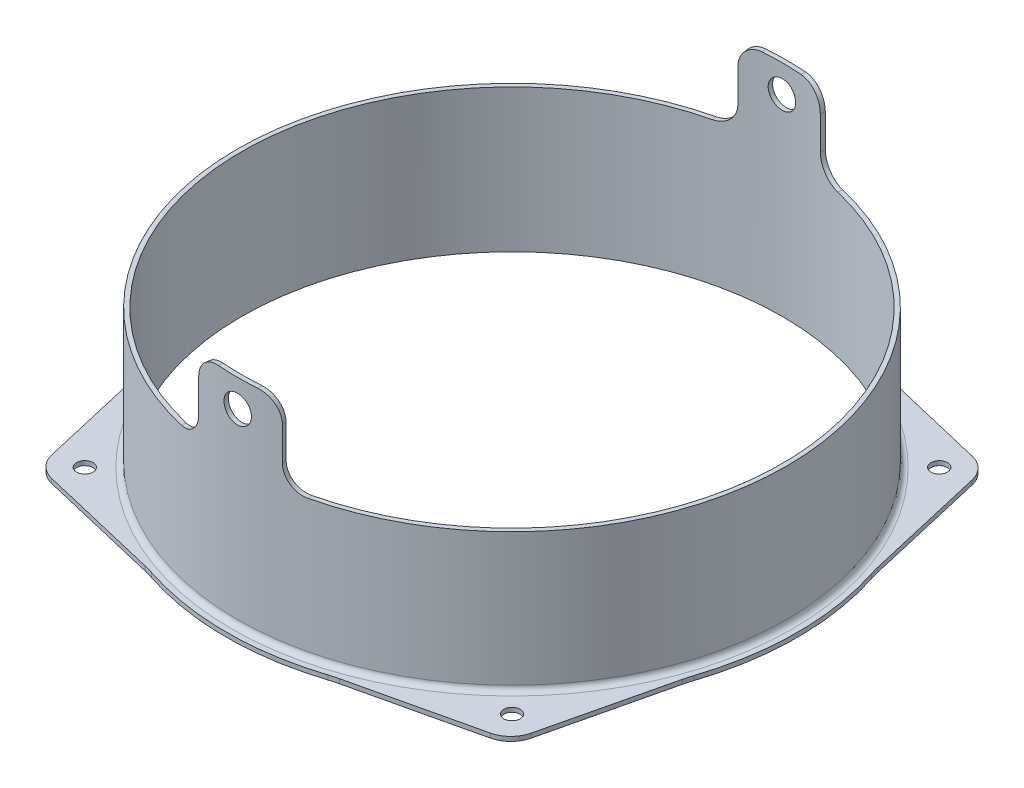
SolidWorks part; units mm, degrees
material "Stainless Steel (ferritic)"
ref_plane "Front Plane" through (0, 0, 0) normal (0, 0, 1) x (1, 0, 0)
ref_plane "Top Plane" through (0, 0, 0) normal (0, 1, 0) x (1, 0, 0)
ref_plane "Right Plane" through (0, 0, 0) normal (1, 0, 0) x (0, 0, -1)
sketch "Sketch1" plane through (0, 0, 0) normal (0, 1, 0) x (1, 0, 0)
  line L0 (17.8971, 48.9297) -> (40.1493, 43.6512)
  line L1 (43.8664, 39.9141) -> (49.0252, 17.6338)
  line L2 (48.9297, -17.8971) -> (43.6512, -40.1493)
  line L3 (39.9141, -43.8664) -> (17.6338, -49.0252)
  line L4 (-17.8971, -48.9297) -> (-40.1493, -43.6512)
  line L5 (-43.8664, -39.9141) -> (-49.0252, -17.6338)
  line L6 (-48.9297, 17.8971) -> (-43.6512, 40.1493)
  line L7 (-39.9141, 43.8664) -> (-17.6338, 49.0252)
  line L8 (0.1397, 51.9998) -> (-0.1397, -51.9998) construction
  line L9 (-51.9998, 0.1397) -> (51.9998, -0.1397) construction
  line L10 (0, 38.8907) -> (0, -38.8907) construction
  line L11 (-38.8907, 38.8907) -> (38.8907, 38.8907) construction
  line L12 (-38.8907, 38.8907) -> (-38.8907, -38.8907) construction
  line L13 (-38.8907, -38.8907) -> (38.8907, -38.8907) construction
  line L14 (38.8907, 38.8907) -> (38.8907, -38.8907) construction
  line L15 (-38.8907, 0) -> (38.8907, 0) construction
  circle A0 centre (0, 0) radius 49.2
  circle A1 centre (0, 0) radius 50
  arc A2 (-17.6338, 49.0252) -> (-15.9939, 49.4792) centre (-22.1454, 68.5097) ccw
  arc A3 (0.1397, 51.9998) -> (-15.9939, 49.4792) centre (0, 0) ccw
  arc A4 (16.2596, 49.3926) -> (0.1397, 51.9998) centre (0, 0) ccw
  arc A5 (16.2596, 49.3926) -> (17.8971, 48.9297) centre (22.5132, 68.3897) ccw
  arc A6 (43.8664, 39.9141) -> (40.1493, 43.6512) centre (38.9952, 38.7862) ccw
  arc A7 (49.0252, 17.6338) -> (49.4792, 15.9939) centre (68.5097, 22.1454) ccw
  arc A8 (49.3926, -16.2596) -> (49.4792, 15.9939) centre (0, 0) ccw
  arc A9 (49.3926, -16.2596) -> (48.9297, -17.8971) centre (68.3897, -22.5132) ccw
  arc A10 (39.9141, -43.8664) -> (43.6512, -40.1493) centre (38.7862, -38.9952) ccw
  arc A11 (17.6338, -49.0252) -> (15.9939, -49.4792) centre (22.1454, -68.5097) ccw
  arc A12 (-16.2596, -49.3926) -> (15.9939, -49.4792) centre (0, 0) ccw
  arc A13 (-16.2596, -49.3926) -> (-17.8971, -48.9297) centre (-22.5132, -68.3897) ccw
  arc A14 (-43.8664, -39.9141) -> (-40.1493, -43.6512) centre (-38.9952, -38.7862) ccw
  arc A15 (-49.0252, -17.6338) -> (-49.4792, -15.9939) centre (-68.5097, -22.1454) ccw
  arc A16 (-49.3926, 16.2596) -> (-49.4792, -15.9939) centre (0, 0) ccw
  arc A17 (-49.3926, 16.2596) -> (-48.9297, 17.8971) centre (-68.3897, 22.5132) ccw
  arc A18 (-39.9141, 43.8664) -> (-43.6512, 40.1493) centre (-38.7862, 38.9952) ccw
  circle A21 centre (-38.8907, 38.8907) radius 1.5
  circle A22 centre (38.8907, 38.8907) radius 1.5
  circle A23 centre (38.8907, -38.8907) radius 1.5
  circle A24 centre (-38.8907, -38.8907) radius 1.5
  point P19 (0, 0)
  point P62 (0, 0)
  dimension "D1" = 98.4
  dimension "D2" = 100
  dimension "D3" = 3
  dimension "D4" = 77.7814
extrude "Boss-Extrude1" add sketch "Sketch1" along normal blind 0.8 contours A1 | A24 | A23 | A22 | A21 | L7 A2 A3 A4 A5 L0 A6 L1 A7 A8 A9 L2 A10 L3 A11 A12 A13 L4 A14 L5 A15 A16 A17 L6 A18
extrude "Boss-Extrude3" add sketch "Sketch1<4>" along normal blind 40 contours A0 | A1
sketch "Sketch1<4>" plane through (0, 0, 0) normal (0, 1, 0) x (1, 0, 0) same geometry as "Sketch1"
fillet "Fillet1" radius 1 1 edges at (0, 0.8, 50)
ref_plane "Plane3" through (0, 40, 0) normal (0, 1, 0) x (1, 0, 0)
sketch "Sketch10" plane through (0, 40, 0) normal (0, 1, 0) x (1, 0, 0)
  line L0 (0, 0) -> (-7.6219, 49.4157)
  line L1 (0, 0) -> (-7.6219, -49.4157)
  line L2 (0, 50) -> (0, -50) construction
  line L3 (-50, 0) -> (50, 0) construction
  circle A0 centre (0, 0) radius 50 construction
  arc A1 (-7.6219, 49.4157) -> (-7.6219, -49.4157) centre (0, 0) ccw
  dimension "D1" = 162.464
extrude "Cut-Extrude1" cut sketch "Sketch10" against normal blind 14
sketch "Sketch11" plane through (0, 40, 0) normal (0, 1, 0) x (1, 0, 0)
  line L0 (0, 0) -> (7.6219, 49.4157)
  line L1 (0, 50) -> (0, -50) construction
  line L2 (0, 0) -> (7.6219, -49.4157)
  circle A0 centre (0, 0) radius 50 construction
  arc A1 (7.6219, -49.4157) -> (7.6219, 49.4157) centre (0, 0) ccw
  dimension "D1" = 162.464
extrude "Cut-Extrude2" cut sketch "Sketch11" against normal blind 14
fillet "Fillet2" radius 4 4 edges at (-7.5609, 26, -49.0203) (7.5609, 26, -49.0203) (7.5609, 26, 49.0203) (-7.5609, 26, 49.0203)
fillet "Fillet4" radius 4 4 edges at (7.5609, 40, -49.0203) (-7.5609, 40, -49.0203) (7.5609, 40, 49.0203) (-7.5609, 40, 49.0203)
sketch "Sketch16" plane through (0, 0, 0) normal (0, 0, 1) x (1, 0, 0)
  line L0 (7.6219, 30) -> (7.6219, 36) construction
  line L1 (-7.6219, 30) -> (-7.6219, 36) construction
  line L2 (3.6442, 40) -> (-3.6442, 40) construction
  line L3 (7.6219, 30) -> (7.6219, 36) construction
  line L4 (-7.6219, 30) -> (-7.6219, 36) construction
  line L5 (3.6442, 40) -> (-3.6442, 40) construction
  line L6 (-7.6219, 30) -> (7.6219, 30) construction
  line L7 (0, 40) -> (0, 30) construction
  circle A0 centre (0, 35) radius 2.5
  spline S0 degree 3 poles (-1946.8355, -385.9645) (-249.3838, -62.5741) (12.7828, 10.1269) (7.4958, 37.0354) (7.4198, 37.2894) (7.2211, 37.7739) (7.0995, 38.0036) (6.812, 38.4385) (6.6446, 38.6443) (6.2785, 39.0133) (6.0787, 39.1788) (5.6443, 39.4711) (5.4129, 39.5953) (4.934, 39.7947) (4.6834, 39.8713) (-33.4157, 47.4819) (-136.2893, -499.2381) (-375.0346, -1923.343) knots -12.908112 -12.908112 -12.908112 -12.908112 0.125 0.125 0.25 0.25 0.375 0.375 0.5 0.5 0.625 0.625 0.75 0.75 0.875 0.875 19.242757 19.242757 19.242757 19.242757 only from (7.6219, 36) to (3.6442, 40) construction
  spline S1 degree 3 poles (434.6243, -1910.8766) (98.0903, -226.527) (22.4966, 45.2694) (-4.6762, 39.8731) (-4.9291, 39.7965) (-5.4112, 39.5963) (-5.6397, 39.4737) (-6.0719, 39.1839) (-6.2764, 39.0152) (-6.6427, 38.6465) (-6.807, 38.4453) (-7.097, 38.0082) (-7.2202, 37.7755) (-7.418, 37.2944) (-7.4941, 37.0426) (-14.6986, 0.5863) (477.2703, -92.2407) (1962.6953, -303.4903) knots -13.087079 -13.087079 -13.087079 -13.087079 0.125 0.125 0.25 0.25 0.375 0.375 0.5 0.5 0.625 0.625 0.75 0.75 0.875 0.875 18.380121 18.380121 18.380121 18.380121 only from (-3.6442, 40) to (-7.6219, 36) construction
  spline S2 degree 3 poles (7.6219, 36) (7.6219, 36.2643) (7.5963, 36.5241) (7.4958, 37.0354) (7.4198, 37.2894) (7.2211, 37.7739) (7.0995, 38.0036) (6.812, 38.4385) (6.6446, 38.6443) (6.2785, 39.0133) (6.0787, 39.1788) (5.6443, 39.4711) (5.4129, 39.5953) (4.934, 39.7947) (4.6834, 39.8713) (4.1683, 39.9742) (3.9078, 40) (3.6442, 40) knots 0 0 0 0 0.125 0.125 0.25 0.25 0.375 0.375 0.5 0.5 0.625 0.625 0.75 0.75 0.875 0.875 1 1 1 1 construction
  spline S3 degree 3 poles (-3.6442, 40) (-3.9078, 40) (-4.1668, 39.9742) (-4.6762, 39.8731) (-4.9291, 39.7965) (-5.4112, 39.5963) (-5.6397, 39.4737) (-6.0719, 39.1839) (-6.2764, 39.0152) (-6.6427, 38.6465) (-6.807, 38.4453) (-7.097, 38.0082) (-7.2202, 37.7755) (-7.418, 37.2944) (-7.4941, 37.0426) (-7.5963, 36.5256) (-7.6219, 36.2643) (-7.6219, 36) knots 0 0 0 0 0.125 0.125 0.25 0.25 0.375 0.375 0.5 0.5 0.625 0.625 0.75 0.75 0.875 0.875 1 1 1 1 construction
  dimension "D1" = 5
  dimension "D2" = 2.5
extrude "Cut-Extrude3" cut sketch "Sketch16" against normal through all both and the other way through all
